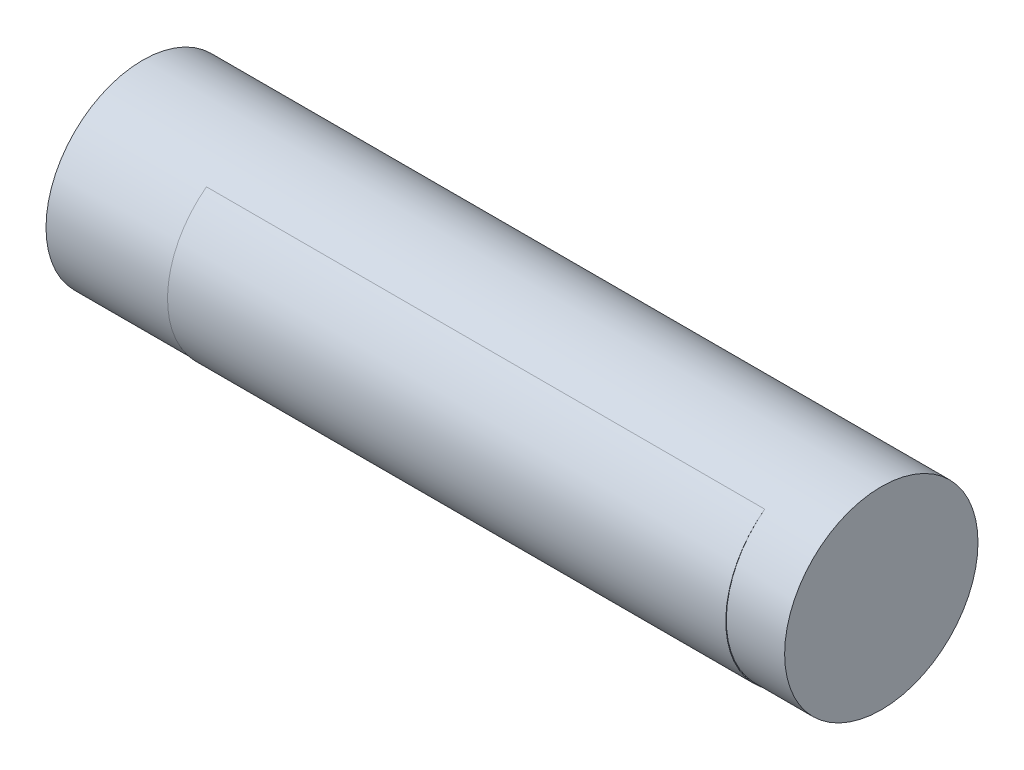
SolidWorks part; units mm, degrees
ref_plane "Front Plane" through (0, 0, 0) normal (0, 0, 1) x (1, 0, 0)
ref_plane "Top Plane" through (0, 0, 0) normal (0, 1, 0) x (1, 0, 0)
ref_plane "Right Plane" through (0, 0, 0) normal (1, 0, 0) x (0, 0, -1)
sketch "Sketch1" plane through (0, 0, 0) normal (0, 0, 1) x (1, 0, 0)
  line L1 (-49.0995, 3.8023) -> (60.9005, 3.8023)
  line L2 (-49.0995, 3.8023) -> (-49.0995, -15.2477)
  line L3 (-49.0995, -15.2477) -> (60.9005, -15.2477)
  line L4 (60.9005, 3.8023) -> (60.9005, -15.2477)
revolve "Revolve1" add sketch "Sketch1" angle 360 about L1
sketch3d "3DSketch1"
  circle A2 centre (0, 3.882, -0.1063) radius 19.05
  point P2 (19.05, 3.882, -0.1063)
  point P3 (0, 3.882, -0.1063)
extrude "Boss-Extrude1" add sketch "3DSketch1" along direction (1, 0, 0) on the side of the normal blind 72.39 and the other way blind 73.152
sketch "Sketch3" plane through (72.39, 0, 0) normal (1, 0, 0) x (0, 0, -1)
  line L0 (0.1063, 22.932) -> (0.1063, -15.168)
  circle A0 centre (0.1063, 3.882) radius 19.05 construction
sketch3d "3DSketch3"
  line L0 (-73.152, 3.1131, 0) -> (72.628, 3.1131, 0)
